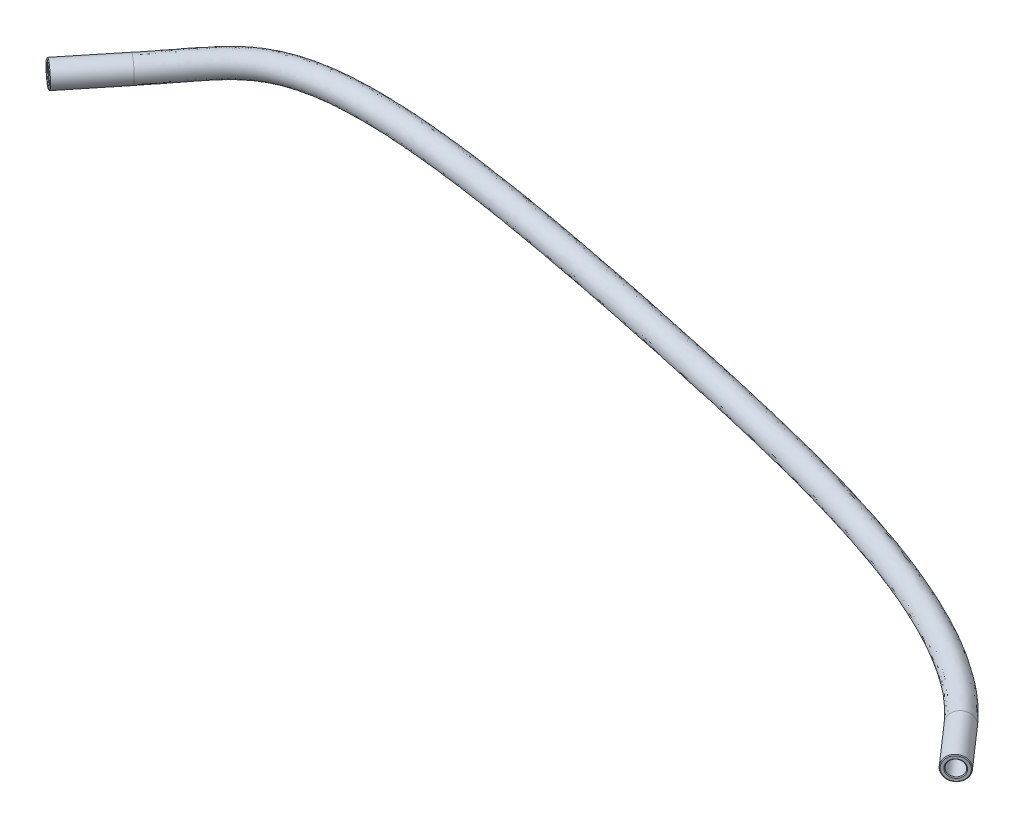
SolidWorks part; units mm, degrees
ref_plane "Front Plane" through (0, 0, 0) normal (0, 0, 1) x (1, 0, 0)
ref_plane "Top Plane" through (0, 0, 0) normal (0, 1, 0) x (1, 0, 0)
ref_plane "Right Plane" through (0, 0, 0) normal (1, 0, 0) x (0, 0, -1)
sketch3d "3DSketch1"
  line L0 (154.1644, -99.6875, 10.8405) -> (148.1041, -99.6875, 3.9186)
  line L1 (-17.8376, -99.5875, -21.9249) -> (-24.2514, -99.5875, -13.9938)
  spline S0 degree 3 poles (148.1041, -99.6875, 3.9186) (133.9328, -99.6875, -12.2675) (31.3858, -99.6746, -36.7382) (-6.3844, -99.6246, -39.5244) (-12.8888, -99.5875, -28.0444) (-17.8376, -99.5875, -21.9249) knots 0 0 0 0 0.258762 0.768958 1 1 1 1
sketch "Sketch1" plane through (67.5912, 0, 77.2008) normal (-0.6587, 0, -0.7524) x (-0.7524, 0, 0.6587)
  circle A0 centre (-108.8494, -99.6875) radius 2
  circle A1 centre (-108.8494, -99.6875) radius 1.3
  circle A2 centre (-108.8494, -99.6875) radius 3.5524 construction
  dimension "D1" = 2.6
  dimension "D2" = 4
sweep "Sweep1" add profiles "Sketch1" path "3DSketch1"
chamfer "Chamfer1" distance 0.127 angle 45 4 edges at (-22.6963, -99.5909, -12.7362) (-23.2406, -99.5897, -13.1764) (152.6597, -99.6875, 12.158) (153.1863, -99.6875, 11.6968)
